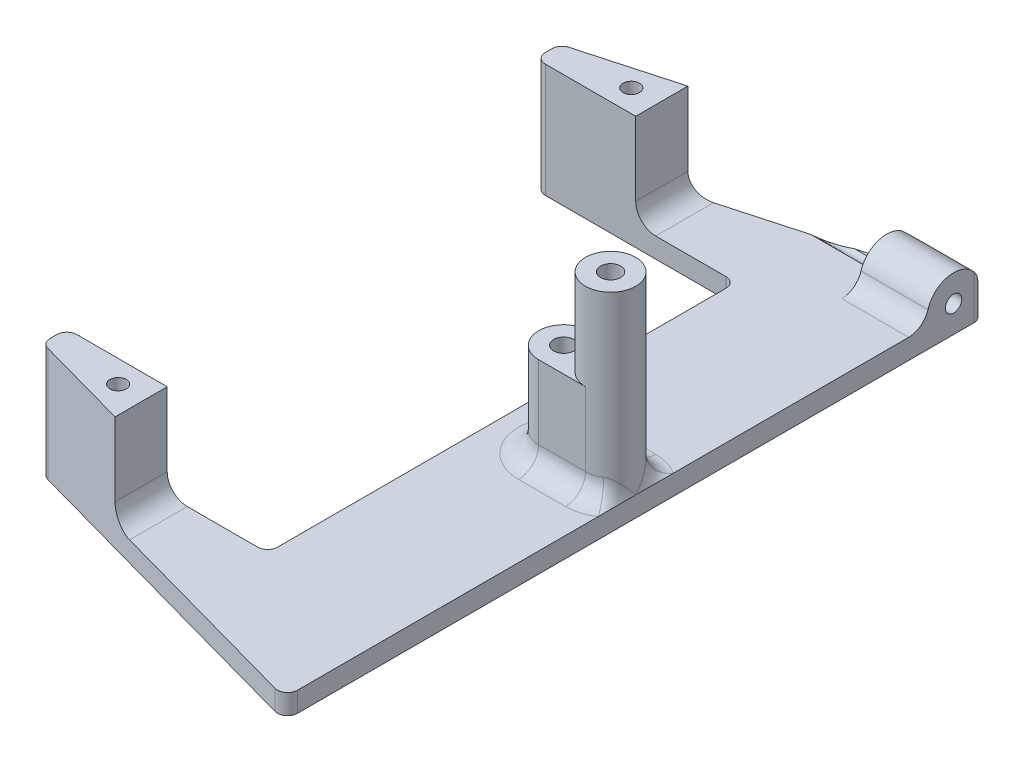
SolidWorks part; units mm, degrees
ref_plane "Front Plane" through (0, 0, 0) normal (0, 0, 1) x (1, 0, 0)
ref_plane "Top Plane" through (0, 0, 0) normal (0, 1, 0) x (1, 0, 0)
ref_plane "Right Plane" through (0, 0, 0) normal (1, 0, 0) x (0, 0, -1)
sketch "Sketch1" plane through (0, 0, 0) normal (0, 1, 0) x (1, 0, 0)
  line L0 (0, 0) -> (7, 0)
  line L1 (0, 3.75) -> (7, 3.75)
  line L2 (0, -3.75) -> (7, -3.75)
  circle A0 centre (0, 0) radius 3.75
  circle A1 centre (7, 0) radius 3.75
  dimension "D1" = 7.5
  dimension "D2" = 7
extrude "Boss-Extrude2" add sketch "Sketch1" along normal blind 30 contours A1 A0 | A1 A0 | A1 A0 L2 | A1 L1 A0 | L0 A1 A0 | A0 A1 L0 region at (3.5, 0, -0.5072) region at (-0.0731, 0, 0) region at (3.5, 0, 0.5072) region at (7.0731, 0, 0) region at (3.5, 0, -3.0985) region at (3.5, 0, 3.0985)
sketch "Sketch4" plane through (0, 30, 0) normal (0, 1, 0) x (1, 0, 0)
  line L2 (7, 3.75) -> (0, 3.75)
  line L3 (0, -3.75) -> (7, -3.75)
  line L4 (7, 3.75) -> (0, 3.75)
  line L5 (0, -3.75) -> (7, -3.75)
  circle A0 centre (7, 0) radius 3.75
  arc A3 (0, 3.75) -> (0, -3.75) centre (0, 0) ccw
  arc A4 (7, -3.75) -> (7, 3.75) centre (7, 0) ccw
  arc A5 (0, 3.75) -> (0, -3.75) centre (0, 0) ccw
  arc A6 (7, -3.75) -> (7, 3.75) centre (7, 0) ccw
  line M6 (7, 3.75) -> (0, 3.75)
  arc M7 (0, 3.75) -> (0, -3.75) centre (0, 0) ccw
  line M8 (0, -3.75) -> (7, -3.75)
  dimension "D1" = 0
extrude "Cut-Extrude3" cut sketch "Sketch4" against normal blind 13 contours A0 M6 M7 M8 region at (0.5548, 30, 0)
sketch "Sketch5" plane through (0, 0, 0) normal (0, -1, 0) x (1, 0, 0)
  line L0 (10.75, 0) -> (10.75, -52.5)
  line L1 (10.75, -52.5) -> (-39.25, -38.6338)
  line L2 (-39.25, -38.6338) -> (-39.25, -35)
  line L3 (-39.25, -35) -> (-9.25, -35)
  line L4 (-9.25, -35) -> (-9.25, 35)
  line L5 (-9.25, 35) -> (-39.25, 35)
  line L6 (-39.25, 35) -> (-39.25, 38.6338)
  line L7 (-39.25, 38.6338) -> (10.75, 52.5)
  line L8 (10.75, 52.5) -> (10.75, 0)
  arc A0 (7, -3.75) -> (7, 3.75) centre (7, 0) ccw construction
  dimension "D1" = 50
  dimension "D2" = 105
  dimension "D3" = 74.5
  dimension "D4" = 70
  dimension "D5" = 30
extrude "Boss-Extrude3" add sketch "Sketch5" against normal blind 3
sketch "Sketch6" plane through (0, 3, 0) normal (0, 1, 0) x (1, 0, 0)
  line L46 (-24.25, -42.7936) -> (-24.25, 42.7936)
  line L54 (10.75, 52.5) -> (-39.25, 38.6338)
  line L55 (10.75, -52.5) -> (10.75, 52.5)
  line L56 (-39.25, -38.6338) -> (10.75, -52.5)
  line L57 (-39.25, -35) -> (-39.25, -38.6338)
  line L58 (-9.25, -35) -> (-39.25, -35)
  line L59 (-9.25, 35) -> (-9.25, -35)
  line L60 (-39.25, 35) -> (-9.25, 35)
  line L61 (-39.25, 38.6338) -> (-39.25, 35)
  line L62 (10.75, 52.5) -> (-39.25, 38.6338)
  line L63 (10.75, -52.5) -> (10.75, 52.5)
  line L64 (-39.25, -38.6338) -> (10.75, -52.5)
  line L65 (-39.25, -35) -> (-39.25, -38.6338)
  line L66 (-9.25, -35) -> (-39.25, -35)
  line L67 (-9.25, 35) -> (-9.25, -35)
  line L68 (-39.25, 35) -> (-9.25, 35)
  line L69 (-39.25, 38.6338) -> (-39.25, 35)
  line M12 (10.75, 52.5) -> (-39.25, 38.6338)
  line M13 (-39.25, 38.6338) -> (-39.25, 35)
  line M14 (-39.25, 35) -> (-9.25, 35)
  line M16 (-9.25, -35) -> (-39.25, -35)
  line M17 (-39.25, -35) -> (-39.25, -38.6338)
  line M18 (-39.25, -38.6338) -> (10.75, -52.5)
  dimension "D2" = 15
  dimension "D1" = 0
extrude "Boss-Extrude4" add sketch "Sketch6" along normal blind 14 contours L46 M18 M16 M17 | L46 M14 M12 M13 region at (-30.8399, 3, 37.983) region at (-30.8399, 3, -37.983)
sketch "Sketch7" plane through (0, 17, 0) normal (0, 1, 0) x (1, 0, 0)
  line L0 (-39.25, 38.6338) -> (-39.25, -38.6338)
  line L1 (-39.25, -38.6338) -> (-24.25, -42.7936)
  line L2 (-24.25, -42.7936) -> (2.25, -42.7936)
  line L3 (2.25, -42.7936) -> (2.25, 42.7936)
  line L4 (2.25, 42.7936) -> (-24.25, 42.7936)
  line L5 (-24.25, 42.7936) -> (-39.25, 38.6338)
  dimension "D1" = 41.5
extrude "Boss-Extrude5" add sketch "Sketch7" along normal blind 3
sketch "Sketch8" plane through (0, 20, 0) normal (0, 1, 0) x (1, 0, 0)
  line L0 (-28.25, 38.3422) -> (-28.25, 35)
  line L3 (-24.25, -42.7936) -> (-24.25, 42.7936)
  line L4 (-28.25, 38.3422) -> (-28.25, 41.6843)
  line L5 (-28.25, -41.6843) -> (-28.25, -38.3422)
  line L6 (-28.25, -38.3422) -> (-28.25, -35)
  line L11 (10.75, 52.5) -> (-39.25, 38.6338)
  line L12 (10.75, -52.5) -> (10.75, 52.5)
  line L13 (-39.25, -38.6338) -> (10.75, -52.5)
  line L14 (-39.25, -35) -> (-39.25, -38.6338)
  line L15 (-9.25, -35) -> (-39.25, -35)
  line L16 (-9.25, 35) -> (-9.25, -35)
  line L17 (-39.25, 35) -> (-9.25, 35)
  line L18 (-39.25, 38.6338) -> (-39.25, 35)
  line L19 (10.75, 52.5) -> (-39.25, 38.6338)
  line L20 (10.75, -52.5) -> (10.75, 52.5)
  line L21 (-39.25, -38.6338) -> (10.75, -52.5)
  line L22 (-39.25, -35) -> (-39.25, -38.6338)
  line L23 (-9.25, -35) -> (-39.25, -35)
  line L24 (-9.25, 35) -> (-9.25, -35)
  line L25 (-39.25, 35) -> (-9.25, 35)
  line L26 (-39.25, 38.6338) -> (-39.25, 35)
  circle A0 centre (-28.25, -38.3422) radius 1.225
  circle A1 centre (-28.25, 38.3422) radius 1.225
  dimension "D1" = 2.45
  dimension "D3" = 4
  dimension "D2" = 0
extrude "Cut-Extrude4" cut sketch "Sketch8" against normal through all contours A1 | A0
sketch "Sketch3" plane through (0, 0, 0) normal (0, -1, 0) x (1, 0, 0)
  circle A0 centre (0, 0) radius 1.5
  dimension "D1" = 3
extrude "Cut-Extrude2" cut sketch "Sketch3" against normal through all
sketch "Sketch2" plane through (0, 30, 0) normal (0, 1, 0) x (1, 0, 0)
  circle A0 centre (7, 0) radius 1.5
  dimension "D1" = 3
extrude "Cut-Extrude1" cut sketch "Sketch2" against normal blind 30
sketch "Sketch9" plane through (2.25, 0, 0) normal (1, 0, 0) x (0, 0, -1)
  line L0 (3.75, 17) -> (42.7936, 17) construction
  line L1 (4.7936, 34) -> (14.7936, 34)
  line L2 (4.7936, 34) -> (4.7936, 17)
  line L3 (4.7936, 17) -> (14.7936, 17)
  line L4 (14.7936, 34) -> (14.7936, 17)
  line L6 (42.7936, 20) -> (42.7936, 17) construction
  dimension "D1" = 28
  dimension "D2" = 10
  dimension "D3" = 17
extrude "Boss-Extrude6" add sketch "Sketch9" along normal blind 8.5
sketch "Sketch11" plane through (10.75, 0, 0) normal (1, 0, 0) x (0, 0, -1)
  line L0 (43.5, 3) -> (43.5, 4)
  line L1 (51.5, 4) -> (51.5, 3)
  line L5 (-52.5, 0) -> (52.5, 0)
  line L6 (52.5, 0) -> (52.5, 3)
  line L7 (52.5, 3) -> (0, 3)
  line L8 (0, 3) -> (-52.5, 3)
  line L9 (-52.5, 3) -> (-52.5, 0)
  line L10 (-52.5, 0) -> (52.5, 0)
  line L11 (52.5, 0) -> (52.5, 3)
  line L12 (52.5, 3) -> (0, 3)
  line L13 (0, 3) -> (-52.5, 3)
  line L14 (-52.5, 3) -> (-52.5, 0)
  arc A0 (43.5, 4) -> (51.5, 4) centre (47.5, 4) cw
  circle A1 centre (47.5, 4) radius 1.225
  line M8 (52.5, 3) -> (0, 3)
  dimension "D4" = 4
  dimension "D5" = 2.45
  dimension "D2" = 1
  dimension "D3" = 5
  dimension "D1" = 0
extrude "Boss-Extrude7" add sketch "Sketch11" against normal blind 10 contours A0 L0 L1 A1 M8 region at (10.75, 5.3421, -47.5)
sketch "Sketch12" plane through (0, 3, 0) normal (0, -1, 0) x (1, 0, 0)
  line L3 (7.1441, -51.5) -> (0.75, -49.7268)
  line L4 (0.75, -49.7268) -> (0.75, -51.5)
  line L5 (0.75, -51.5) -> (7.1441, -51.5)
  line L6 (7.1441, -51.5) -> (0.75, -49.7268)
  line L7 (0.75, -49.7268) -> (0.75, -51.5)
  line L8 (0.75, -51.5) -> (7.1441, -51.5)
  dimension "D1" = 0
extrude "Cut-Extrude6" cut sketch "Sketch12" against normal blind 10
sketch "Sketch13" plane through (0, 0, -14.7936) normal (0, 0, -1) x (-1, 0, 0)
  line L0 (-7.75, 34) -> (-7.75, 25.5)
  line L1 (-2.25, 20) -> (1.5008, 20)
  line L5 (-2.25, 17) -> (-2.25, 20)
  line L6 (-2.25, 20) -> (-2.25, 34)
  line L7 (-2.25, 34) -> (-10.75, 34)
  line L8 (-10.75, 34) -> (-10.75, 17)
  line L9 (-10.75, 17) -> (-2.25, 17)
  line L10 (-2.25, 17) -> (-2.25, 20)
  line L11 (-2.25, 20) -> (-2.25, 34)
  line L12 (-2.25, 34) -> (-10.75, 34)
  line L13 (-10.75, 34) -> (-10.75, 17)
  line L14 (-10.75, 17) -> (-2.25, 17)
  arc A0 (-7.75, 25.5) -> (-2.25, 20) centre (-2.25, 25.5) ccw
  line M7 (-2.25, 20) -> (-2.25, 34)
  line M8 (-2.25, 34) -> (-10.75, 34)
  dimension "D2" = 3
  dimension "D1" = 0
extrude "Cut-Extrude7" cut sketch "Sketch13" against normal up to next contours L0 A0 M7 M8 region at (4.8599, 27.5314, -14.7936)
sketch "Sketch14" plane through (10.75, 0, 0) normal (1, 0, 0) x (0, 0, -1)
  line L0 (14.7936, 34) -> (4.7936, 34) construction
  line L1 (4.7936, 34) -> (4.7936, 17) construction
  circle A0 centre (9.1236, 29.69) radius 0.875
  dimension "D3" = 1.75
  dimension "D1" = 4.31
  dimension "D2" = 4.33
extrude "Cut-Extrude8" cut sketch "Sketch14" against normal blind 10 contours A0
sketch "Sketch15" plane through (0, 20, 0) normal (0, 1, 0) x (1, 0, 0)
  line L0 (-39.25, -25.7936) -> (-17.25, -25.7936)
  line L1 (-39.25, 38.6338) -> (-39.25, -38.6338) construction
  line L2 (-17.25, -25.7936) -> (-17.25, -42.7936)
  line L4 (-24.25, -42.7936) -> (2.25, -42.7936) construction
  line L13 (-24.25, 42.7936) -> (-39.25, 38.6338)
  line L14 (-39.25, 38.6338) -> (-39.25, -38.6338)
  line L15 (-39.25, -38.6338) -> (-24.25, -42.7936)
  line L16 (-24.25, -42.7936) -> (2.25, -42.7936)
  line L17 (2.25, -42.7936) -> (2.25, 4.7936)
  line L18 (2.25, 4.7936) -> (2.25, 14.7936)
  line L19 (2.25, 14.7936) -> (2.25, 42.7936)
  line L20 (2.25, 42.7936) -> (-24.25, 42.7936)
  line L21 (-24.25, 42.7936) -> (-39.25, 38.6338)
  line L22 (-39.25, 38.6338) -> (-39.25, -38.6338)
  line L23 (-39.25, -38.6338) -> (-24.25, -42.7936)
  line L24 (-24.25, -42.7936) -> (2.25, -42.7936)
  line L25 (2.25, -42.7936) -> (2.25, 4.7936)
  line L26 (2.25, 4.7936) -> (2.25, 14.7936)
  line L27 (2.25, 14.7936) -> (2.25, 42.7936)
  line L28 (2.25, 42.7936) -> (-24.25, 42.7936)
  circle M12 centre (-28.25, -38.3422) radius 1.225
  line M15 (-39.25, 38.6338) -> (-39.25, -38.6338)
  line M16 (-39.25, -38.6338) -> (-24.25, -42.7936)
  line M17 (-24.25, -42.7936) -> (2.25, -42.7936)
  dimension "D1" = 22
  dimension "D2" = 17
  dimension "D3" = 0
extrude "Boss-Extrude8" add sketch "Sketch15" along normal blind 20 contours L2 L0 M15 M16 M17 M12 region at (-27.6963, 20, 33.5808)
sketch "Sketch16" plane through (-17.25, 0, 0) normal (1, 0, 0) x (0, 0, -1)
  line L0 (-25.7936, 40) -> (-25.7936, 20) construction
  line L1 (-42.7936, 40) -> (-25.7936, 40)
  line L2 (-42.7936, 40) -> (-42.7936, 35)
  line L3 (-42.7936, 35) -> (-25.7936, 35)
  line L4 (-25.7936, 40) -> (-25.7936, 35)
  dimension "D1" = 5
extrude "Boss-Extrude9" add sketch "Sketch16" along normal blind 25
sketch "Sketch17" plane through (0, 40, 0) normal (0, 1, 0) x (1, 0, 0)
  line L0 (-0.25, -34.2936) -> (7.75, -34.2936)
  line L1 (7.75, -25.7936) -> (7.75, -42.7936) construction
  circle A0 centre (-0.25, -34.2936) radius 6.25
  dimension "D1" = 12.5
  dimension "D2" = 8
extrude "Cut-Extrude9" cut sketch "Sketch17" against normal up to next contours A0
sketch "Sketch18" plane through (0, 40, 0) normal (0, 1, 0) x (1, 0, 0)
  circle A0 centre (-0.25, -34.2936) radius 11.6726
  circle A1 centre (-0.25, -34.2936) radius 6.25 construction
  circle A2 centre (-0.25, -34.2936) radius 6.25
extrude "Boss-Extrude10" add sketch "Sketch18" against normal up to surface (5 mm away) up to face at (-0.25, 35, 40.5436)
fillet "Fillet1" radius 3 1 edges at (-17.25, 35, 34.2936)
sketch "Sketch19" plane through (0, 20, 0) normal (0, 1, 0) x (1, 0, 0)
  line L1 (2.25, -42.7936) -> (-16.75, -42.7936)
  line L2 (2.25, -42.7936) -> (2.25, -24.7936)
  line L3 (2.25, -24.7936) -> (-16.75, -24.7936)
  line L4 (-16.75, -42.7936) -> (-16.75, -24.7936)
  dimension "D1" = 19
  dimension "D2" = 18
extrude "Cut-Extrude10" cut sketch "Sketch19" against normal up to next
fillet "Fillet2" radius 3 8 edges at (9.6517, 3, 2.6517) (9.6517, 3, -2.6517) (3.5, 3, -3.75) (-3.75, 3, 0) (-24.25, 3, -38.8968) (5.75, 3, -43.5) (-24.25, 3, 38.8968) (3.5, 3, 3.75)
fillet "Fillet3" radius 1.5 8 edges at (2.25, 18.5, 24.7936) (-16.75, 18.5, 24.7936) (-8.25, 37.5, 25.7936) (-39.25, 30, 25.7936) (-39.25, 20, 38.6338) (-39.25, 10, -38.6338)
sketch "Sketch23" plane through (10.75, 0, 0) normal (1, 0, 0) x (0, 0, -1)
  line L0 (-23.2936, 17) -> (-61.4436, 17)
  line L1 (-77.5338, -21.5176) -> (93.6122, -21.5176)
  line L2 (-77.5338, -21.5176) -> (-77.5338, 69.4558)
  line L3 (-77.5338, 69.4558) -> (93.6122, 69.4558)
  line L4 (93.6122, -21.5176) -> (93.6122, 69.4558)
  line L5 (-61.4436, 17) -> (-62.6991, -11.0529)
  line L6 (-62.6991, -11.0529) -> (69.7595, -7.805)
  line L7 (69.7595, -7.805) -> (62.5358, 17)
  line L8 (62.5358, 17) -> (4.7936, 17)
  line L10 (4.7936, 20) -> (-23.2936, 20)
  line L11 (-23.2936, 20) -> (-23.2936, 17)
  line L12 (-23.2936, 17) -> (-3.75, 17)
  line L13 (-3.75, 17) -> (3.75, 17)
  line L14 (3.75, 17) -> (4.7936, 17)
  line L15 (4.7936, 17) -> (4.7936, 20)
  line L16 (4.7936, 20) -> (-23.2936, 20)
  line L17 (-23.2936, 20) -> (-23.2936, 17)
  line L18 (-23.2936, 17) -> (-3.75, 17)
  line L19 (-3.75, 17) -> (3.75, 17)
  line L20 (3.75, 17) -> (4.7936, 17)
  line L21 (4.7936, 17) -> (4.7936, 20)
  line L22 (-7.1441, 35.0737) -> (4.7936, 35.0737)
  line L23 (-7.1441, 35.0737) -> (-7.1441, 17)
  line L24 (-7.1441, 17) -> (4.7936, 17)
  line L25 (14.7936, 20) -> (14.7936, 17)
  line L26 (14.7936, 17) -> (42.7936, 17)
  line L27 (42.7936, 17) -> (42.7936, 20)
  line L28 (42.7936, 20) -> (14.7936, 20)
  line L29 (14.7936, 20) -> (14.7936, 17)
  line L30 (14.7936, 17) -> (42.7936, 17)
  line L31 (42.7936, 17) -> (42.7936, 20)
  line L32 (42.7936, 20) -> (14.7936, 20)
  line L33 (4.7936, 35.0737) -> (4.7936, 17)
  dimension "D1" = 0
  dimension "D2" = 0
extrude "Cut-Extrude13" cut sketch "Sketch23" against normal through all contours L1 L4 L3 L2 L22 L33 L21 L8 L29 L32 L31 L7 L6 L5 L0 L17 L16 L23 | L23 L16 L17 L18 | L31 L32 L29 L8 region at (10.75, 18.5, 15.2189) region at (10.75, 18.5, -28.7936) region at (10.75, 29.8316, -10.2358)
sketch "Sketch24" plane through (0, 20, 0) normal (0, 1, 0) x (1, 0, 0)
  line L4 (2.25, 4.7936) -> (-39.25, 4.7936)
  line L5 (-39.25, 4.7936) -> (-39.25, -7.1441)
  line L6 (-39.25, -7.1441) -> (2.25, -7.1441)
  line L7 (2.25, -7.1441) -> (2.25, 4.7936)
  line L8 (2.25, 4.7936) -> (-39.25, 4.7936)
  line L9 (-39.25, 4.7936) -> (-39.25, -7.1441)
  line L10 (-39.25, -7.1441) -> (2.25, -7.1441)
  line L11 (2.25, -7.1441) -> (2.25, 4.7936)
  dimension "D1" = 0
extrude "Cut-Extrude14" cut sketch "Sketch24" against normal up to surface (3 mm away)
sketch "Sketch25" plane through (10.75, 0, 0) normal (1, 0, 0) x (0, 0, -1)
  circle A0 centre (47.5, 4) radius 1.225
  dimension "D1" = 2.45
extrude "Cut-Extrude15" cut sketch "Sketch25" against normal through all
fillet "Fillet4" radius 1.5 4 edges at (-9.25, 1.5, -35) (-9.25, 1.5, 35) (10.75, 1.5, 52.5) (10.75, 1.5, -52.5)
